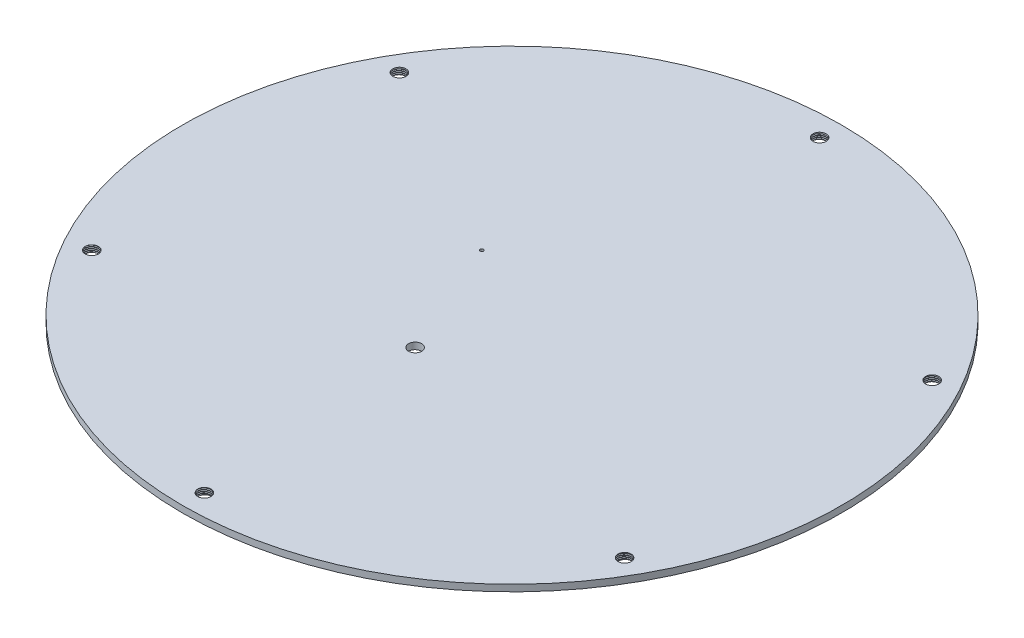
SolidWorks part; units mm, degrees
material "1060 Alloy"
ref_plane "Front Plane" through (0, 0, 0) normal (0, 0, 1) x (1, 0, 0)
ref_plane "Top Plane" through (0, 0, 0) normal (0, 1, 0) x (1, 0, 0)
ref_plane "Right Plane" through (0, 0, 0) normal (1, 0, 0) x (0, 0, -1)
sketch "Sketch1" plane through (0, 0, 0) normal (0, 1, 0) x (1, 0, 0)
  circle A0 centre (0, 0) radius 50
  circle A1 centre (0, 46.67) radius 1
  circle A2 centre (40.4174, 23.335) radius 1
  circle A3 centre (40.4174, -23.335) radius 1
  circle A4 centre (0, -46.67) radius 1
  circle A5 centre (-40.4174, -23.335) radius 1
  circle A6 centre (-40.4174, 23.335) radius 1
  point P17 (0, 0)
  dimension "D1" = 100
  dimension "D2" = 2
  dimension "D3" = 46.67
  dimension "D4" = 6
extrude "Boss-Extrude1" add sketch "Sketch1" along normal blind 1
thread "Thread1" pitch 0.25 method cut profile "Thread Profile1" start angle 0, offset 0, length 10, pitch 0.25, diameter 2
ref_plane "Plane1" through (-41.4174, 1, 23.335) normal (0, 0, 1) x (-1, 0, 0)
sketch "Thread Profile1" plane through (-41.4174, 1, 23.335) normal (0, 0, 1) x (-1, 0, 0)
  line L0 (0, 0) -> (0, 0.25) construction
  line L1 (0, 0) -> (0.1353, 0.0781)
  line L2 (0.1353, 0.0781) -> (0.1353, 0.1094)
  line L3 (0.1353, 0.1094) -> (0, 0.1875)
  line L4 (0.1353, 0.0937) -> (0, 0.0937) construction
  line L11 (0, 0) -> (0, 0.1875)
  point P2 (0, 0)
  dimension "Pitch" = 0.25
  dimension "Profile_Angle" = 60
  dimension "Profile_Land" = 0.0312
  dimension "Profile_Height" = 0.1353
pattern_circular "CirPattern1" count 6 over 360 about axis through (0, 0, 0) along (0, 1, 0) of "Thread1"
sketch "Sketch2" plane through (0, 1, 0) normal (0, 1, 0) x (1, 0, 0)
  line L0 (12.1829, 21.1013) -> (0, 0) construction
  line L1 (0, 0) -> (-13.509, -23.3983) construction
  line L2 (0, 0) -> (-7.5117, -28.0339) construction
  line L3 (0, 0) -> (0, -23.2906) construction
  line L4 (0, -23.2906) -> (0, 0) construction
  line L5 (0, 0) -> (-12.9568, 7.4806) construction
  circle A1 centre (-3.1058, -11.5911) radius 1
  circle A2 centre (-10.8253, 6.25) radius 0.25
  point P10 (0, 0)
  dimension "D1" = 0.5
  dimension "D3" = 2
  dimension "D2" = 12.5
  dimension "D4" = 12
  dimension "D5" = 15
  dimension "D6" = 30
  dimension "D7" = 90
  dimension "D8" = 0
extrude "Cut-Extrude1" cut sketch "Sketch2" against normal through all both and the other way through all
